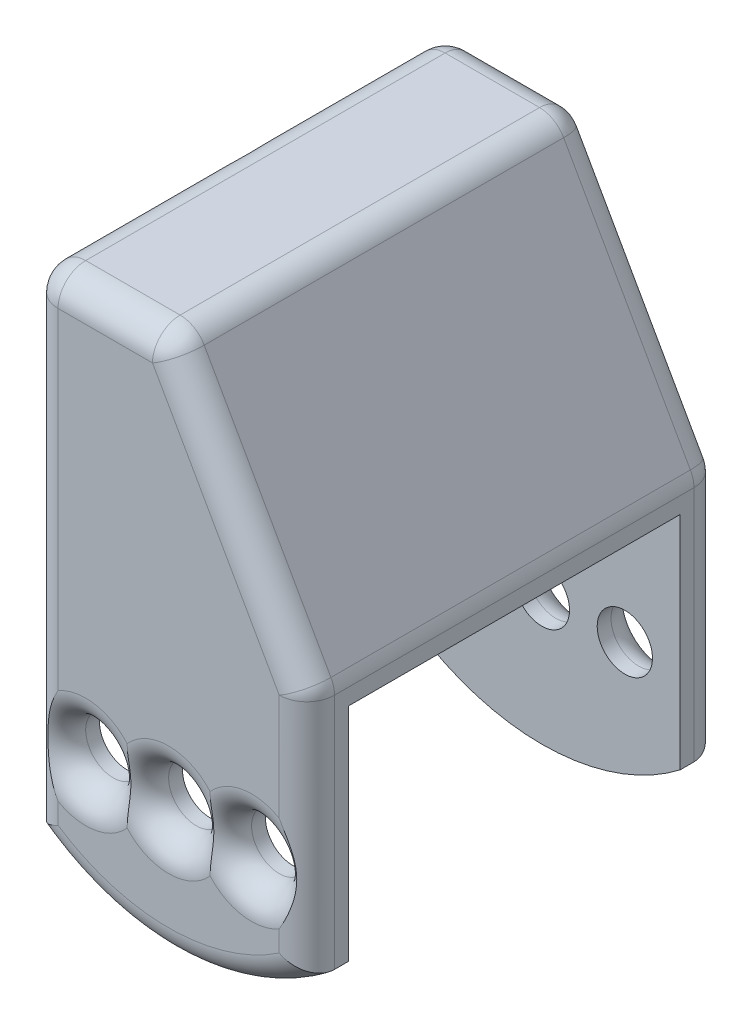
SolidWorks part; units mm, degrees
ref_plane "Front Plane" through (0, 0, 0) normal (0, 0, 1) x (1, 0, 0)
ref_plane "Top Plane" through (0, 0, 0) normal (0, 1, 0) x (1, 0, 0)
ref_plane "Right Plane" through (0, 0, 0) normal (1, 0, 0) x (0, 0, -1)
sketch "Sketch1" plane through (0, 0, 0) normal (0, 0, 1) x (1, 0, 0)
  line L0 (0, 0) -> (-10, -13.0323) construction
  line L1 (0, 0) -> (10, -13.0323) construction
  line L2 (-10, -13.0323) -> (10, -13.0323) construction
  line L9 (-10, 22.3777) -> (0, 22.3777)
  line L10 (-10, -13.0323) -> (-10, 22.3777)
  line L11 (10, 4.6727) -> (10, -13.0323)
  line L12 (0, 22.3777) -> (10, 4.6727)
  arc A0 (-10, -13.0323) -> (10, -13.0323) centre (0, 0) ccw
  circle A2 centre (0, -7.0323) radius 2
  circle A3 centre (6, -7.0323) radius 2
  circle A4 centre (-6, -7.0323) radius 2
  dimension "D6" = 4
  dimension "D7" = 4
  dimension "D10" = 4
  dimension "D1" = 75
  dimension "D2" = 20
  dimension "D3" = 35.41
  dimension "D5" = 6
  dimension "D8" = 6
  dimension "D9" = 6
extrude "Boss-Extrude1" add sketch "Sketch1" along normal blind 30
sketch "Sketch2" plane through (10, 0, 0) normal (1, 0, 0) x (0, 0, -1)
  line L0 (-30, -16.4268) -> (0, -16.4268) construction
  line L1 (-27, -16.4268) -> (-3, -16.4268)
  line L2 (-27, -16.4268) -> (-27, 2.9677)
  line L3 (-27, 2.9677) -> (-3, 2.9677)
  line L4 (-3, -16.4268) -> (-3, 2.9677)
  line L5 (-30, -13.0323) -> (-30, -16.4268) construction
  line L6 (0, -16.4268) -> (0, -13.0323) construction
  line L7 (-30, -13.0323) -> (0, -13.0323) construction
  dimension "D1" = 3
  dimension "D2" = 3
  dimension "D3" = 16
extrude "Cut-Extrude1" cut sketch "Sketch2" against normal through all
sketch "Sketch3" plane through (-10, 0, 0) normal (-1, 0, 0) x (0, 0, 1)
  line L0 (3, 2.9677) -> (27, 2.9677) construction
  circle A0 centre (15, 12.9677) radius 9
  circle A1 centre (15, 12.9677) radius 6 construction
  circle A2 centre (15, 18.9677) radius 2
  circle A3 centre (15, 6.9677) radius 2
  circle A4 centre (9, 12.9677) radius 2
  circle A5 centre (21, 12.9677) radius 2
  point P5 (15, 2.9677)
  dimension "D1" = 18
  dimension "D2" = 10
  dimension "D3" = 12
  dimension "D4" = 4
  dimension "D5" = 4
  dimension "D6" = 4
  dimension "D7" = 4
extrude "Cut-Extrude2" cut sketch "Sketch3" against normal blind 3
fillet "Fillet1" radius 2 19 edges at (-10, 22.3777, 15) (-4, -7.0323, 0) (8, -7.0323, 0) (2, -7.0323, 0) (-5, 22.3777, 0) (-10, 4.6727, 0) (0, -16.4268, 0) (10, -4.1798, 0) (-4, -7.0323, 30) (2, -7.0323, 30) (10, -4.1798, 30) (0, -16.4268, 30) (-10, 4.6727, 30) (-5, 22.3777, 30) (8, -7.0323, 30) (10, 4.6727, 15) (5, 13.5252, 30) (0, 22.3777, 15) (5, 13.5252, 0)
